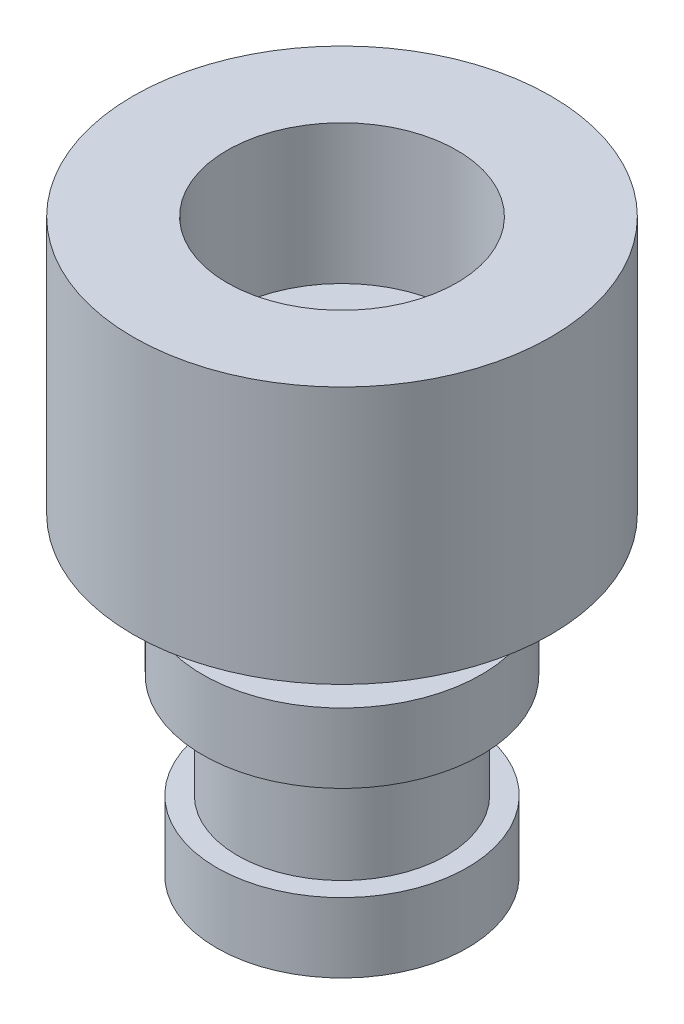
SolidWorks part; units mm, degrees
ref_plane "Front Plane" through (0, 0, 0) normal (0, 0, 1) x (1, 0, 0)
ref_plane "Top Plane" through (0, 0, 0) normal (0, 1, 0) x (1, 0, 0)
ref_plane "Right Plane" through (0, 0, 0) normal (1, 0, 0) x (0, 0, -1)
sketch "Sketch1" plane through (0, 0, 0) normal (0, 1, 0) x (1, 0, 0)
  circle A0 centre (-0.522, 0.5111) radius 1.6
  circle A1 centre (-0.522, 0.5111) radius 3
  dimension "D1" = 3.2
  dimension "D2" = 6
extrude "Boss-Extrude1" add sketch "Sketch1" along normal blind 3.7 contours A1
extrude "Boss-Extrude2" add sketch "Sketch1<3>" along normal blind 1 contours A0 region at (-0.522, 0, -0.5111)
sketch "Sketch1<3>" plane through (0, 0, 0) normal (0, 1, 0) x (1, 0, 0) same geometry as "Sketch1"
sketch "Sketch5" plane through (0, 0, 0) normal (0, -1, 0) x (1, 0, 0)
  circle A2 centre (-0.522, -0.5111) radius 1.5
  circle A3 centre (-0.522, -0.5111) radius 1.5
  dimension "D2" = 3
  dimension "D1" = 1.5
extrude "Boss-Extrude3" add sketch "Sketch5" along normal blind 1 contours A3
sketch "Sketch6" plane through (0, -1, 0) normal (0, -1, 0) x (1, 0, 0)
  circle A0 centre (-0.522, -0.5111) radius 2
  dimension "D1" = 4
extrude "Boss-Extrude4" add sketch "Sketch6" along normal blind 1
sketch "Sketch8" plane through (0, -2, 0) normal (0, -1, 0) x (-1, 0, 0)
  circle A0 centre (0.522, 0.5111) radius 1.5
  dimension "D1" = 3
extrude "Boss-Extrude5" add sketch "Sketch8" along normal blind 2.5 contours A0
sketch "Sketch10" plane through (0, -4.5, 0) normal (0, -1, 0) x (1, 0, 0)
  circle A0 centre (-0.522, -0.5111) radius 1.8
extrude "Boss-Extrude6" add sketch "Sketch10" against normal blind 1
sketch "Sketch11" plane through (0, 3.7, 0) normal (0, 1, 0) x (1, 0, 0)
  text T0 "VIII" font "Century Gothic" height in points 5
sketch "Sketch12" plane through (0, 3.7, 0) normal (0, 1, 0) x (1, 0, 0)
  circle A0 centre (-0.522, 0.5111) radius 1.65
extrude "Cut-Extrude1" cut sketch "Sketch12" against normal blind 2
